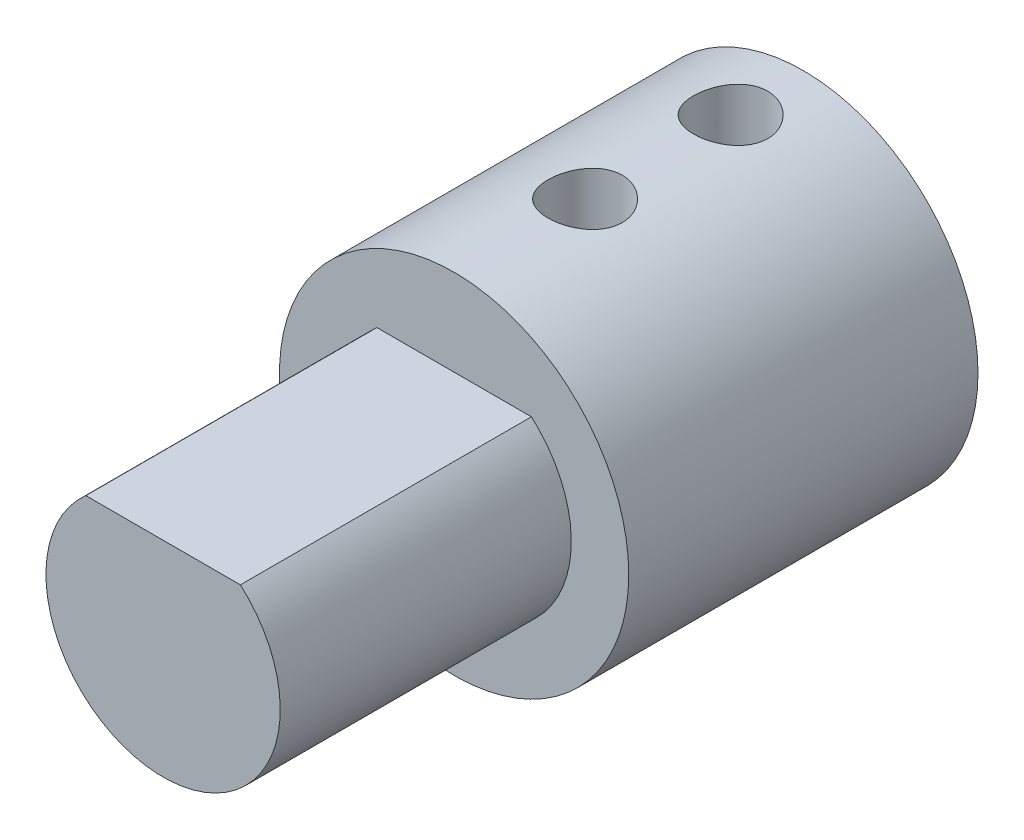
SolidWorks part; units mm, degrees
ref_plane "Front" through (0, 0, 0) normal (0, 0, 1) x (1, 0, 0)
ref_plane "Top" through (0, 0, 0) normal (0, 1, 0) x (1, 0, 0)
ref_plane "Right" through (0, 0, 0) normal (1, 0, 0) x (0, 0, -1)
sketch "Sketch1" plane through (0, 0, 0) normal (0, 0, 1) x (1, 0, 0)
  line L0 (-1.5984, 1.475) -> (1.5984, 1.475)
  line L1 (0, 0) -> (0, 1.475) construction
  line L2 (0, 1.475) -> (0, 2.175) construction
  circle A0 centre (0, 0) radius 2.175
  circle A1 centre (0, 0) radius 6
  point P6 (0, -2.175)
  dimension "D1" = 4.35
  dimension "D3" = 12
  dimension "D2" = 3.65
extrude "Boss-Extrude1" add sketch "Sketch1" along normal blind 10 contours A1 A0 | L0 A0 region at (0, 1.7593, 0) region at (-5.8303, 0, 0)
sketch "Sketch3" plane through (0, 0, 0) normal (0, 1, 0) x (1, 0, 0)
  circle A0 centre (0, -2.5) radius 1.275
  circle A1 centre (0, -7.5) radius 1.275
  dimension "D1" = 2.55
  dimension "D2" = 2.5
  dimension "D3" = 5
extrude "Cut-Extrude1" cut sketch "Sketch3" along normal up to next
sketch "Sketch4" plane through (0, 0, 10) normal (0, 0, 1) x (1, 0, 0)
  circle A0 centre (0, 0) radius 6
  circle A1 centre (0, 0) radius 6 construction
extrude "Boss-Extrude2" add sketch "Sketch4" along normal blind 2
sketch "Sketch6" plane through (0, 0, 12) normal (0, 0, 1) x (1, 0, 0)
  line L0 (-2.6552, 3.025) -> (2.6552, 3.025)
  circle A0 centre (0, 0) radius 4.025
  point P5 (0, -4.025)
  dimension "D1" = 8.05
  dimension "D2" = 7.05
extrude "Boss-Extrude3" add sketch "Sketch6" along normal blind 10 contours L0 A0 region at (0, -0.2641, 12)
